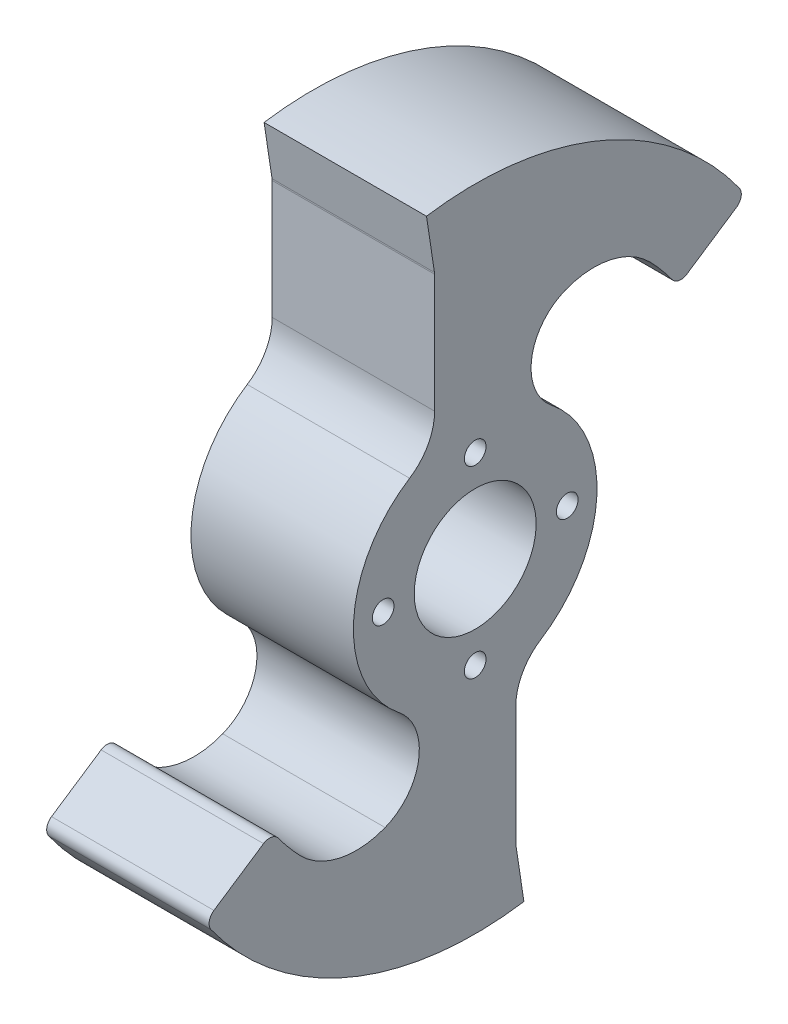
SolidWorks part; units mm, degrees
material "AISI Type A2 Tool Steel"
ref_plane "Front Plane" through (0, 0, 0) normal (0, 0, 1) x (1, 0, 0)
ref_plane "Top Plane" through (0, 0, 0) normal (0, 1, 0) x (1, 0, 0)
ref_plane "Right Plane" through (0, 0, 0) normal (1, 0, 0) x (0, 0, -1)
sketch "Sketch1" plane through (0, 0, 0) normal (1, 0, 0) x (0, 0, -1)
  line L0 (-9.525, 26.9408) -> (-9.525, 62.7816)
  line L1 (-9.525, 62.7816) -> (-11.43, 75.3379)
  line L2 (63.4488, 42.1983) -> (49.6565, 33.0254)
  line L3 (9.525, -26.9408) -> (9.525, -62.7816)
  line L5 (0, 28.575) -> (0, 117.6695) construction
  line L6 (63.4488, 42.1983) -> (124.8998, -50.1987) construction
  line L7 (9.525, -62.7816) -> (11.43, -75.3379)
  line L8 (-63.4488, -42.1983) -> (-49.6565, -33.0254)
  line L10 (0, -28.575) -> (0, -117.6695) construction
  line L11 (-63.4488, -42.1983) -> (-124.8998, 50.1987) construction
  circle A0 centre (0, 0) radius 28.575 construction
  circle A1 centre (0, 0) radius 14.3002
  arc A2 (-11.43, 75.3379) -> (63.4488, 42.1983) centre (0, 0) cw
  arc A3 (46.1967, 33.645) -> (41.1079, 39.7022) centre (0, 0) ccw
  arc A4 (41.1079, 39.7022) -> (9.525, 26.9408) centre (27.8946, 26.9408) ccw
  arc A5 (49.6565, 33.0254) -> (46.1967, 33.645) centre (48.2499, 35.1403) cw
  arc A6 (11.43, -75.3379) -> (-63.4488, -42.1983) centre (0, 0) cw
  arc A7 (-46.1967, -33.645) -> (-41.1079, -39.7022) centre (0, 0) ccw
  arc A8 (-41.1079, -39.7022) -> (-9.525, -26.9408) centre (-27.8946, -26.9408) ccw
  arc A9 (-49.6565, -33.0254) -> (-46.1967, -33.645) centre (-48.2499, -35.1403) cw
  arc A10 (-9.525, 26.9408) -> (-9.525, -26.9408) centre (0, 0) ccw
  arc A11 (9.525, 26.9408) -> (9.525, -26.9408) centre (0, 0) cw
  circle A12 centre (0, 0) radius 9.525
  point P18 (47.5866, 31.6487)
  point P21 (0, 0)
  point P30 (0, 0)
  point P36 (0, 0)
  point P37 (0, 0)
  point P38 (0, 0)
  point P39 (0, 0)
  point P40 (0, 0)
  point P41 (0, 0)
  point P42 (0, 0)
  point P43 (0, 0)
  point P44 (11.43, 40.5154)
  point P45 (0, 0)
  point P46 (11.43, 26.1894)
  dimension "D1" = 57.15
  dimension "D2" = 28.6004
  dimension "D3" = 19.05
  dimension "D4" = 76.2
  dimension "D6" = 65
  dimension "D9" = 2.54
  dimension "D11" = 19.05
  dimension "D5" = 12.7
  dimension "D7" = 19.05
  dimension "D10" = 2
extrude "Boss-Extrude1" add sketch "Sketch1" along normal mid plane 38.1 contours A11 A4 A3 A5 L2 A2 L1 L0 A10 A8 A7 A9 L8 A6 L7 L3 A1 region at (0, 44.8612, 7.5419)
fillet "Fillet1" radius 2.54 4 edges at (0, -42.1983, 63.4488) (0, 42.1983, -63.4488) (0, -62.7816, -9.525) (0, 62.7816, 9.525)
fillet "Fillet2" radius 12.7 4 edges at (0, -26.9408, -9.525) (0, 26.9408, 9.525) (0, -26.9408, 9.525) (0, 26.9408, -9.525)
sketch "Sketch2" plane through (-19.05, 0, 0) normal (-1, 0, 0) x (0, 0, 1)
  circle A0 centre (0, 21.59) radius 2.54
  circle A1 centre (21.59, 0) radius 2.54
  circle A2 centre (0, -21.59) radius 2.54
  circle A3 centre (-21.59, 0) radius 2.54
  point P12 (0, 0)
  dimension "D1" = 5.08
  dimension "D2" = 21.59
  dimension "D3" = 4
extrude "Cut-Extrude1" cut sketch "Sketch2" against normal up to next
